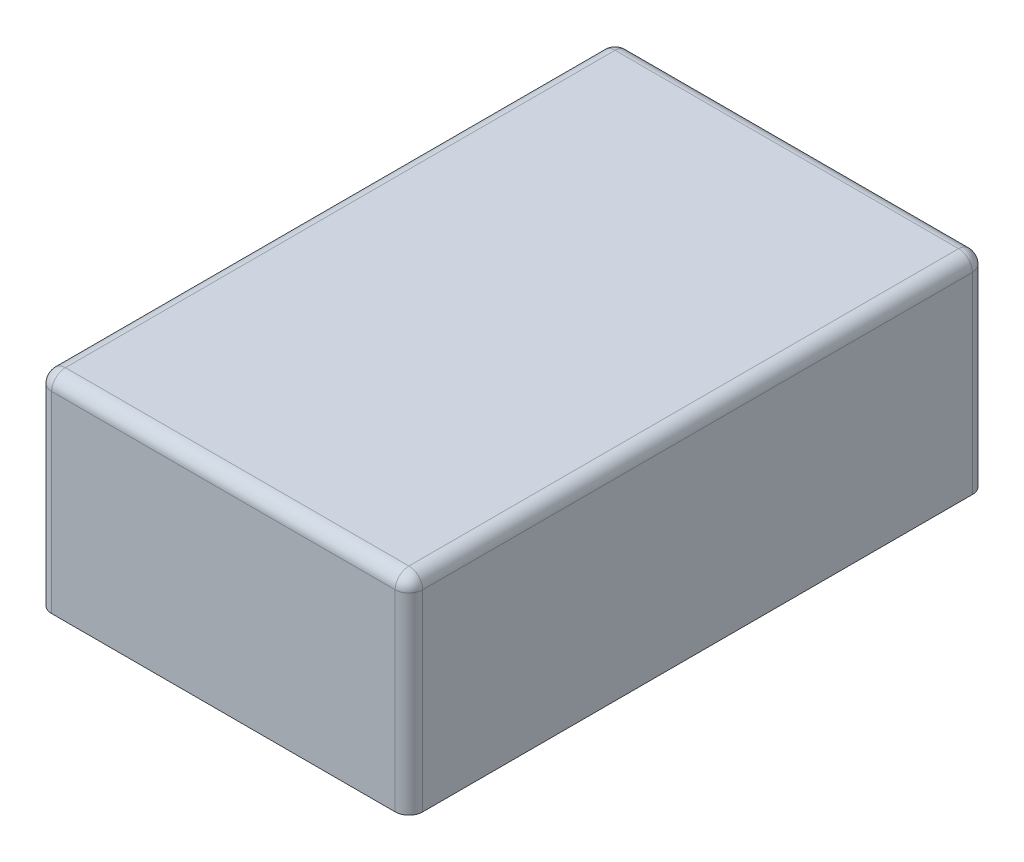
SolidWorks part; units mm, degrees
ref_plane "正面" through (0, 0, 0) normal (0, 0, 1) x (1, 0, 0)
ref_plane "平面" through (0, 0, 0) normal (0, 1, 0) x (1, 0, 0)
ref_plane "右側面" through (0, 0, 0) normal (1, 0, 0) x (0, 0, -1)
sketch "ｽｹｯﾁ1" plane through (0, 0, 0) normal (0, 1, 0) x (1, 0, 0)
  line L0 (-65.7571, 29.7046) -> (-38.7571, 29.7046)
  line L1 (-65.7571, 29.7046) -> (-65.7571, -12.2954)
  line L2 (-38.7571, 29.7046) -> (-38.7571, -12.2954)
  line L3 (-65.7571, -12.2954) -> (-38.7571, -12.2954)
  dimension "D1" = 27
  dimension "D2" = 42
extrude "ﾎﾞｽ - 押し出し1" add sketch "ｽｹｯﾁ1" along normal blind 15
sketch "ｽｹｯﾁ4" plane through (0, 0, 0) normal (0, 1, 0) x (1, 0, 0)
  line L0 (-64.7571, 28.7046) -> (-39.7571, 28.7046)
  line L1 (-64.7571, 28.7046) -> (-64.7571, -11.2954)
  line L2 (-39.7571, 28.7046) -> (-39.7571, -11.2954)
  line L3 (-64.7571, -11.2954) -> (-39.7571, -11.2954)
  dimension "D1" = 25
  dimension "D2" = 40
extrude "ｶｯﾄ - 押し出し1" cut sketch "ｽｹｯﾁ4" along normal blind 14
fillet "ﾌｨﾚｯﾄ1" radius 1 4 edges at (-52.2571, 15, -29.7046) (-38.7571, 15, -8.7046) (-52.2571, 15, 12.2954) (-65.7571, 15, -8.7046)
fillet "ﾌｨﾚｯﾄ3" radius 1 8 edges at (-65.4642, 14.7071, -29.4118) (-39.05, 14.7071, -29.4118) (-65.4642, 14.7071, 12.0025) (-39.05, 14.7071, 12.0025) (-65.7571, 7, -29.7046) (-38.7571, 7, -29.7046) (-65.7571, 7, 12.2954) (-38.7571, 7, 12.2954)
